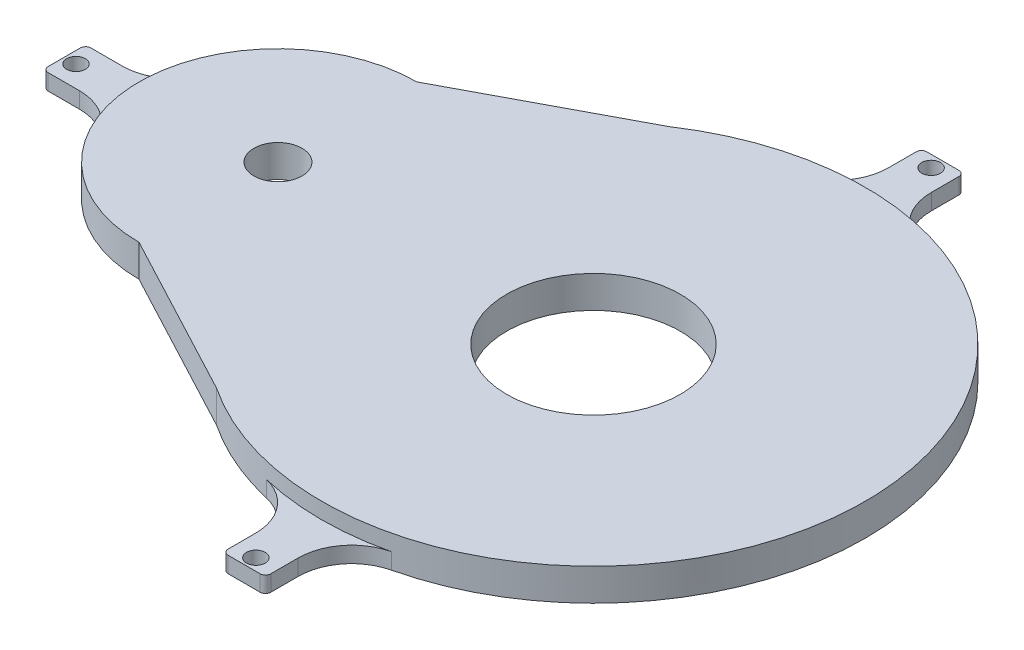
SolidWorks part; units mm, degrees
note: The reader was unsure of these and kept them because the rebuilt part matched: shared geometry of "Sketch1<3>", "Sketch2<11>", "Sketch2<13>", "Sketch2<15>", "Sketch2<16>", "Sketch2<19>", "Sketch2<22>", "Sketch2<23>", "Sketch1<6>".
ref_plane "Front Plane" through (0, 0, 0) normal (0, 0, 1) x (1, 0, 0)
ref_plane "Top Plane" through (0, 0, 0) normal (0, 1, 0) x (1, 0, 0)
ref_plane "Right Plane" through (0, 0, 0) normal (1, 0, 0) x (0, 0, -1)
sketch "Sketch1" plane through (0, 0, 0) normal (0, 1, 0) x (1, 0, 0)
  line L0 (-27.1461, 33.0749) -> (3.7062, 49.4352)
  line L1 (-27.1461, -18.9251) -> (3.7062, -35.2855)
  line L2 (-27.1461, 28.0749) -> (6.7029, 43.7842)
  line L3 (-27.1461, -13.9251) -> (3.7062, -27.3857)
  circle A0 centre (31.9089, 7.0749) radius 44.53
  circle A2 centre (-27.1461, 7.0749) radius 4.5
  circle A3 centre (31.9089, 7.0749) radius 4.5
  circle A4 centre (31.9089, 7.0749) radius 50.89
  arc A5 (-27.1461, -18.9251) -> (-27.1461, 33.0749) centre (-27.1461, 7.0749) cw
  arc A6 (-27.1461, 28.0749) -> (-27.1461, -13.9251) centre (-27.1461, 7.0749) ccw
  circle A7 centre (-14.9861, -5.1851) radius 4.25
  circle A8 centre (31.9089, 7.0749) radius 16.25
  point P16 (-53.1461, 7.0749)
  dimension "D1" = 26
  dimension "D2" = 59.055
  dimension "D3" = 12.16
  dimension "D4" = 12.26
extrude "Boss-Extrude1" add sketch "Sketch1" along normal blind 6 contours A6 L2 A4 L0 A5 L1 L3 | L2 A6 L3 A4 A2 | L2 A4 L3 A0 | A4 L2 A0 L3 | A0 A3 | A7
extrude "Boss-Extrude5" add sketch "Sketch1<3>" along normal blind 6 contours A7 A4 L3 A0
sketch "Sketch1<3>" plane through (0, 0, 0) normal (0, 1, 0) x (1, 0, 0) same geometry as "Sketch1"
sketch "Sketch2" plane through (0, 6, 0) normal (0, 1, 0) x (1, 0, 0)
  line L0 (-27.1461, 33.0749) -> (3.7062, 49.4352)
  line L1 (-27.1461, -18.9251) -> (3.7062, -35.2855)
  line L2 (-27.1461, 28.0749) -> (4.8405, 44.5702)
  line L3 (-27.1461, -13.9251) -> (4.8405, -30.4205)
  line L4 (-53.1461, 7.0749) -> (-67.1461, 7.0749)
  line L9 (82.7989, 7.0749) -> (97.6889, 7.0749)
  line L10 (97.6889, 7.0749) -> (97.6889, 11.0749)
  line L11 (97.6889, 11.0749) -> (82.6415, 11.0749)
  line L12 (97.6889, 7.0749) -> (97.6889, 3.0749)
  line L13 (97.6889, 3.0749) -> (82.6415, 3.0749)
  line L14 (-67.1461, 7.0749) -> (-67.1461, 11.0749)
  line L15 (-67.1461, 11.0749) -> (-52.8365, 11.0749)
  line L16 (-67.1461, 7.0749) -> (-67.1461, 3.0749)
  line L17 (-67.1461, 3.0749) -> (-52.8365, 3.0749)
  line L18 (-67.1461, 7.0749) -> (-68.7461, 7.0749)
  line L19 (-68.7461, 7.0749) -> (-68.7461, 19.0749)
  line L20 (-68.7461, 19.0749) -> (-50.2112, 19.0749)
  line L21 (-68.7461, 7.0749) -> (-68.7461, -4.9251)
  line L22 (-68.7461, -4.9251) -> (-50.2112, -4.9251)
  line L23 (31.9089, 57.9649) -> (31.9089, 72.4649)
  line L24 (31.9089, 72.4649) -> (27.9089, 72.4649)
  line L27 (27.9089, 72.4649) -> (27.9089, 57.8074)
  line L28 (35.9089, 72.4649) -> (35.9089, 57.8074)
  line L29 (31.9089, 72.4649) -> (35.9089, 72.4649)
  line L30 (31.9089, -43.8151) -> (31.9089, -58.3151)
  line L31 (31.9089, -58.3151) -> (35.9089, -58.3151)
  line L34 (31.9089, -58.3151) -> (27.9089, -58.3151)
  line L35 (27.9089, -58.3151) -> (27.9089, -43.6577)
  line L36 (35.9089, -58.3151) -> (35.9089, -43.6577)
  arc A0 (-27.1461, -18.9251) -> (-27.1461, 33.0749) centre (-27.1461, 7.0749) cw
  arc A1 (-27.1461, 33.0749) -> (-27.1461, -18.9251) centre (-27.1461, 7.0749) ccw construction
  arc A2 (31.9089, 57.9649) -> (31.9089, -43.8151) centre (31.9089, 7.0749) cw
  arc A3 (3.7062, -35.2855) -> (3.7062, 49.4352) centre (31.9089, 7.0749) ccw construction
  arc A4 (-27.1461, 28.0749) -> (-27.1461, -13.9251) centre (-27.1461, 7.0749) ccw
  arc A12 (4.8405, 44.5702) -> (4.8405, -30.4205) centre (31.9089, 7.0749) cw
  circle A15 centre (95.4889, 7.0749) radius 1.75
  circle A16 centre (-64.9461, 7.0749) radius 1.75
  circle A17 centre (31.9089, 7.0749) radius 50.89
  circle A18 centre (31.9089, 70.2649) radius 1.75
  circle A19 centre (31.9089, -56.1151) radius 1.75
  arc A20 (27.9089, -43.6577) -> (27.9089, 57.8074) centre (31.9089, 7.0749) ccw
  arc M1 (3.7062, -35.2855) -> (3.7062, 49.4352) centre (31.9089, 7.0749) ccw
  arc M3 (-27.1461, 33.0749) -> (-27.1461, -18.9251) centre (-27.1461, 7.0749) ccw
  dimension "D2" = 14.3095
  dimension "D16" = 2.2
  dimension "D17" = 2.2
  dimension "D3" = 2.2
  dimension "D4" = 2.2
extrude "Boss-Extrude3" add sketch "Sketch2" against normal blind 6 contours A16 L4 L15 L14 M3 | A16 L4 L16 L17 M3 | A15 L9 L10 L11 M1 | A15 L9 L13 L12 M1
extrude "Cut-Extrude1" cut sketch "Sketch2<11>" against normal blind 3 contours A16 L4 L16 L17 M3 | A16 L4 L15 L14 M3
sketch "Sketch2<11>" plane through (0, 6, 0) normal (0, 1, 0) x (1, 0, 0) same geometry as "Sketch2"
extrude "Boss-Extrude4" add sketch "Sketch2<13>" against normal blind 6 contours A15 L9 L13 L12 M1 | A15 L9 L10 L11 M1
sketch "Sketch2<13>" plane through (0, 6, 0) normal (0, 1, 0) x (1, 0, 0) same geometry as "Sketch2"
extrude "Cut-Extrude2" cut sketch "Sketch2<15>" against normal blind 3 contours A15 L9 L13 L12 M1 | A15 L9 L10 L11 M1
sketch "Sketch2<15>" plane through (0, 6, 0) normal (0, 1, 0) x (1, 0, 0) same geometry as "Sketch2"
extrude "Boss-Extrude7" add sketch "Sketch2<16>" against normal blind 3 contours A15 L9 L13 L12 M1 | A15 L9 L10 L11 M1 | A16 L4 L15 L14 M3 | A16 L4 L16 L17 M3
sketch "Sketch2<16>" plane through (0, 6, 0) normal (0, 1, 0) x (1, 0, 0) same geometry as "Sketch2"
extrude "Boss-Extrude9" add sketch "Sketch2<19>" against normal blind 6 contours A19 L30 L35 L34 M1 | A19 L30 L31 L36 M1 | A18 L23 L28 L29 M1 | A18 L23 L24 L27 M1
sketch "Sketch2<19>" plane through (0, 6, 0) normal (0, 1, 0) x (1, 0, 0) same geometry as "Sketch2"
extrude "Cut-Extrude4" cut sketch "Sketch2<22>" against normal blind 3 contours A19 L30 L31 L36 M1 | A19 L30 L35 L34 M1 | A18 L23 L28 L29 M1 | A18 L23 L24 L27 M1 | A16 L4 L15 L14 M3 | A16 L4 L16 L17 M3
sketch "Sketch2<22>" plane through (0, 6, 0) normal (0, 1, 0) x (1, 0, 0) same geometry as "Sketch2"
fillet "Fillet1" radius 1 6 edges at (-67.1461, 1.5, -3.0749) (-67.1461, 1.5, -11.0749) (35.9089, 1.5, -72.4649) (27.9089, 1.5, -72.4649) (27.9089, 1.5, 58.3151) (35.9089, 1.5, 58.3151)
fillet "Fillet2" radius 10 6 edges at (-52.8365, 1.5, -11.0749) (-52.8365, 1.5, -3.0749) (27.9089, 1.5, -57.8074) (35.9089, 1.5, -57.8074) (27.9089, 1.5, 43.6577) (35.9089, 1.5, 43.6577)
extrude "Cut-Extrude5" cut sketch "Sketch2<23>" against normal blind 6 contours A15 L9 L13 L12 M1 | A15 L9 L10 L11 M1
sketch "Sketch2<23>" plane through (0, 6, 0) normal (0, 1, 0) x (1, 0, 0) same geometry as "Sketch2"
extrude "Cut-Extrude8" cut sketch "Sketch1<6>" along normal blind 10 contours A8 A3
sketch "Sketch1<6>" plane through (0, 0, 0) normal (0, 1, 0) x (1, 0, 0) same geometry as "Sketch1"
